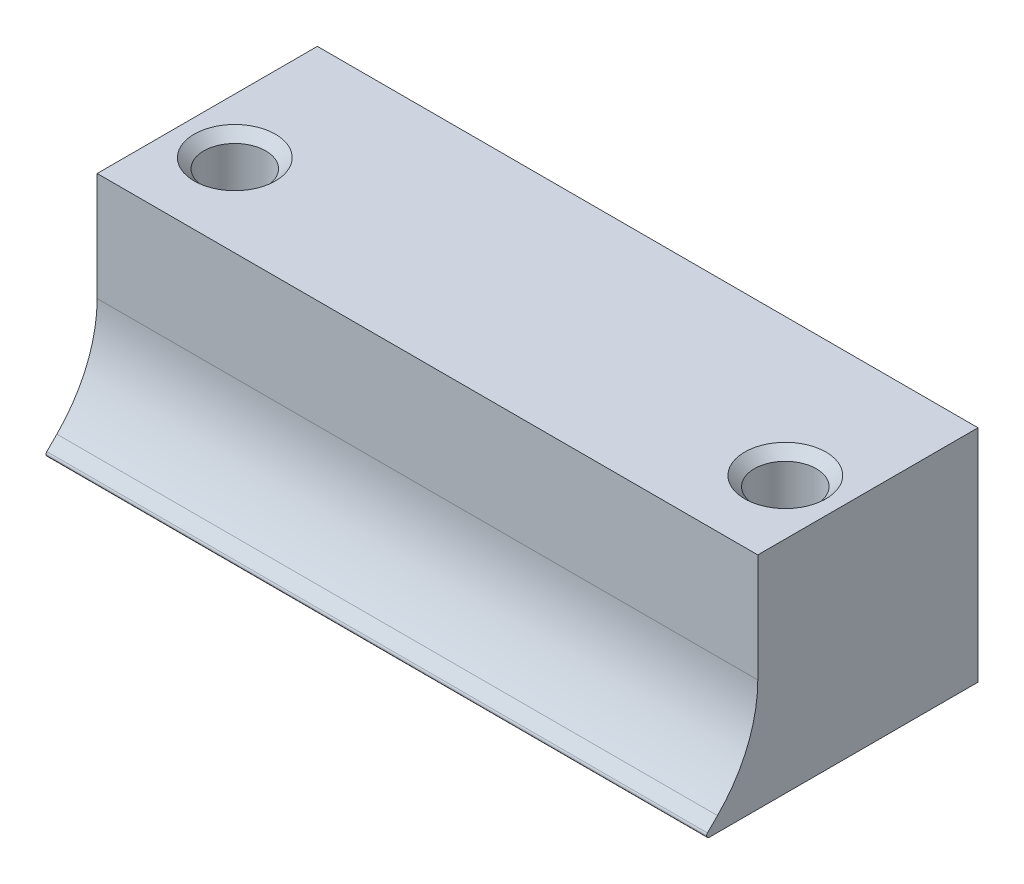
SolidWorks part; units mm, degrees
ref_plane "Front Plane" through (0, 0, 0) normal (0, 0, 1) x (1, 0, 0)
ref_plane "Top Plane" through (0, 0, 0) normal (0, 1, 0) x (1, 0, 0)
ref_plane "Right Plane" through (0, 0, 0) normal (1, 0, 0) x (0, 0, -1)
sketch "Sketch1" plane through (0, 0, 0) normal (1, 0, 0) x (0, 0, -1)
  line L1 (-10, -8.005) -> (10, -8.005)
  line L2 (-10, -8.005) -> (-10, 8.005)
  line L3 (-10, 8.005) -> (10, 8.005)
  line L4 (10, -8.005) -> (10, 8.005)
  line L5 (-10, -8.005) -> (10, 8.005) construction
  line L6 (-10, 8.005) -> (10, -8.005) construction
  point P0 (0, 0)
  dimension "D1" = 16.01
  dimension "D2" = 20
extrude "Boss-Extrude1" add sketch "Sketch1" along normal blind 48
sketch "Sketch2" plane through (0, -8.005, 0) normal (0, -1, 0) x (1, 0, 0)
  line L0 (0, 10) -> (0, -10) construction
  line L2 (0, 0) -> (56.1352, 0) construction
  circle A0 centre (4, 0) radius 2.25
  point P5 (0, 0)
  dimension "D1" = 4
  dimension "D2" = 4.5
extrude "Cut-Extrude1" cut sketch "Sketch2" against normal through all contours A0
chamfer "Chamfer1" distance 0.7 angle 45 2 edges at (4, -8.005, -2.25) (4, 8.005, -2.25)
ref_plane "Plane1" through (24, 0, 0) normal (-1, 0, 0) x (0, 0, 1)
mirror "Mirror1" about plane through (24, 0, 0) normal (-1, 0, 0) of "Chamfer1", "Cut-Extrude1"
sketch "Sketch4" plane through (48, 0, 0) normal (1, 0, 0) x (0, 0, -1)
  line L0 (-6, 8.005) -> (-6, -4.005)
  line L1 (-10, 8.005) -> (-6, 8.005)
  line L2 (-10, 8.005) -> (-10, -8.005)
  line L5 (-6, -4.005) -> (-10, -8.005)
  line L6 (-10, -8.005) -> (10, -8.005) construction
  dimension "D1" = 4
  dimension "D2" = 45
extrude "Cut-Extrude2" cut sketch "Sketch4" against normal through all
fillet "Fillet1" radius 10 1 edges at (24, -4.005, 6) type face fillet first side face at (24, 2, 6) second side face at (24, -6.005, 8)
fillet "Fillet2" radius 0.2 1 edges at (24, -8.005, 10)
